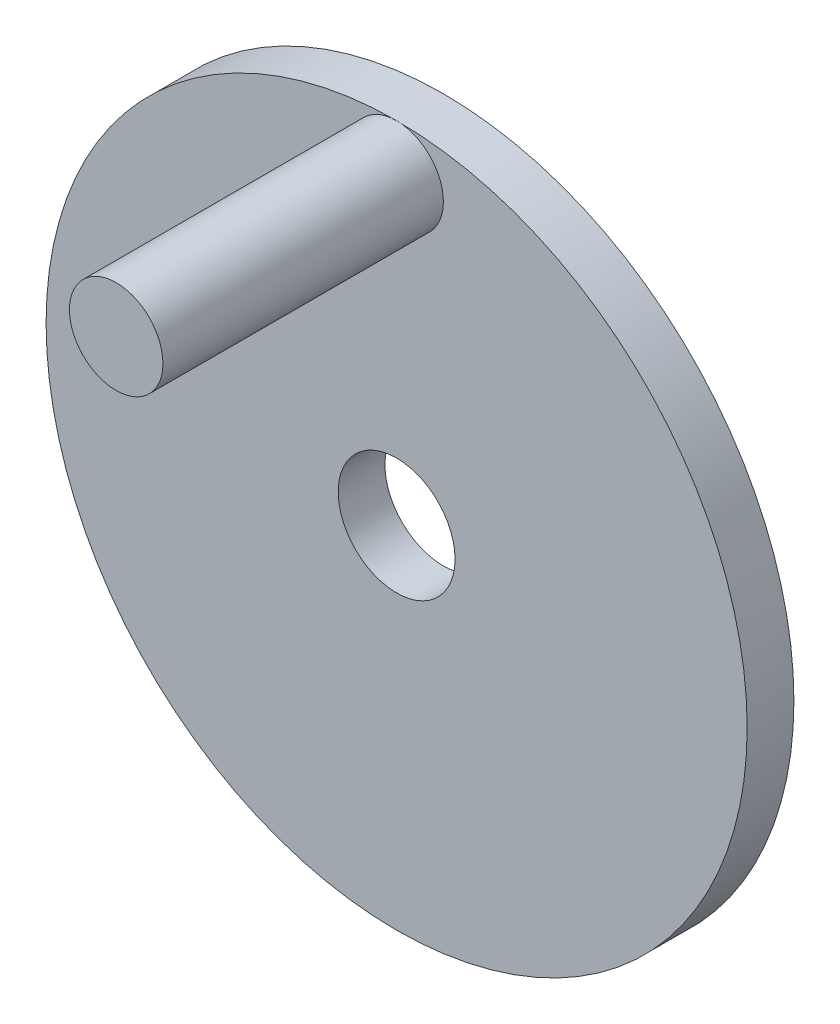
SolidWorks part; units mm, degrees
ref_plane "Front Plane" through (0, 0, 0) normal (0, 0, 1) x (1, 0, 0)
ref_plane "Top Plane" through (0, 0, 0) normal (0, 1, 0) x (1, 0, 0)
ref_plane "Right Plane" through (0, 0, 0) normal (1, 0, 0) x (0, 0, -1)
sketch "Sketch1" plane through (0, 0, 0) normal (0, 0, 1) x (1, 0, 0)
  circle A0 centre (0, 0) radius 19.05
  dimension "D1" = 38.1
extrude "Boss-Extrude1" add sketch "Sketch1" along normal blind 2.54
sketch "Sketch2" plane through (0, 0, 2.54) normal (0, 0, 1) x (1, 0, 0)
  line L0 (0, 0) -> (0, 16.51) construction
  circle A0 centre (0, 16.51) radius 2.54
  circle A1 centre (0, 0) radius 19.05 construction
  dimension "D1" = 5.08
extrude "Boss-Extrude2" add sketch "Sketch2" along normal blind 15.24
sketch "Sketch3" plane through (0, 0, 2.54) normal (0, 0, 1) x (1, 0, 0)
  circle A0 centre (0, 0) radius 3.175
  dimension "D1" = 6.35
extrude "Cut-Extrude1" cut sketch "Sketch3" against normal through all
equation "\"dowel thick\"= 1 / 4"
equation "\"D1@Sketch3\"=\"dowel thick\""
